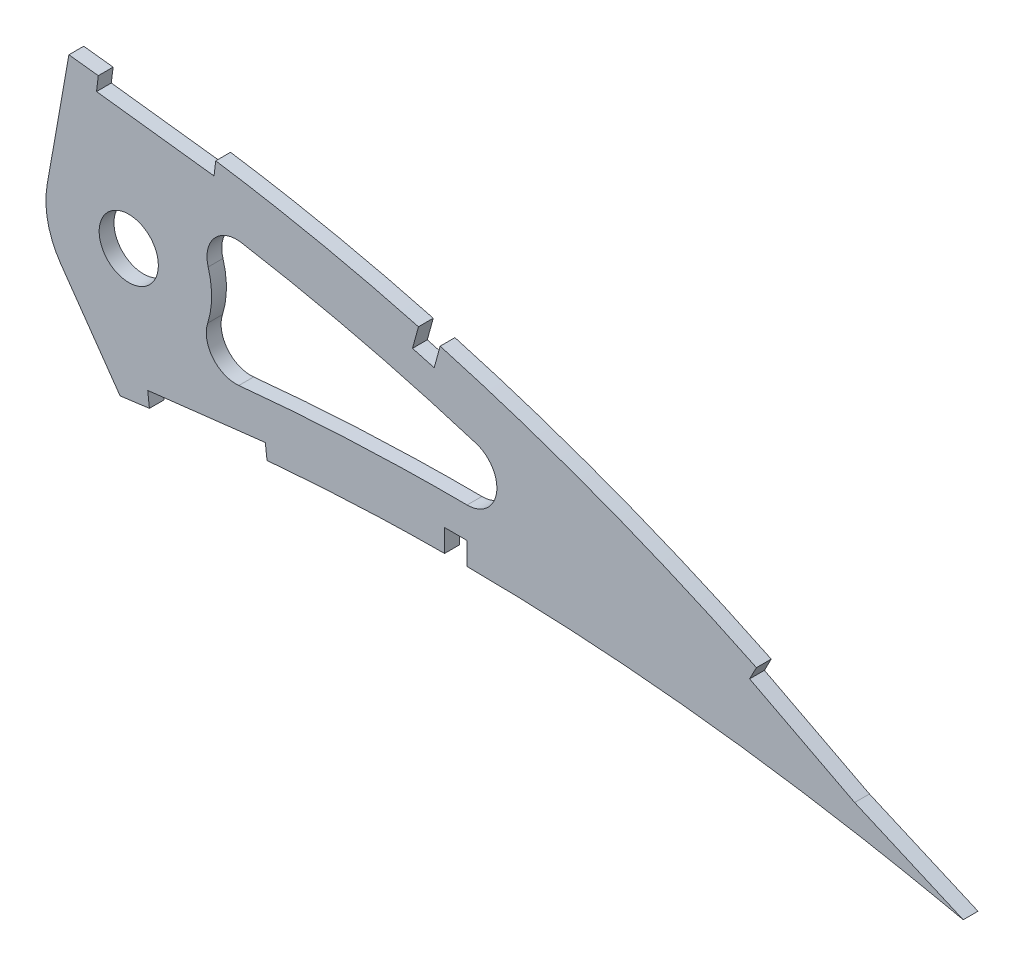
SolidWorks part; units mm, degrees
note: '?' marks a value the reader was unsure of.
material "Pine"
ref_plane "Front Plane" through (0, 0, 0) normal (0, 0, 1) x (1, 0, 0)
ref_plane "Top Plane" through (0, 0, 0) normal (0, 1, 0) x (1, 0, 0)
ref_plane "Right Plane" through (0, 0, 0) normal (1, 0, 0) x (0, 0, -1)
curve "Curve1"
  spline degree 3 poles (554.3197, 0.8642, 0) (554.2772, 0.8904, 0) (554.1075, 0.9953, 0) (553.7252, 1.2298, 0) (553.0885, 1.6204, 0) (552.1972, 2.1644, 0) (551.0519, 2.8603, 0) (549.6522, 3.7033, 0) (547.9988, 4.6906, 0) (546.0922, 5.8176, 0) (543.9326, 7.0789, 0) (541.5207, 8.4695, 0) (538.8569, 9.9815, 0) (535.942, 11.6087, 0) (532.7772, 13.3434, 0) (529.3631, 15.1777, 0) (525.7007, 17.1023, 0) (521.7917, 19.109, 0) (517.6366, 21.1866, 0) (513.2374, 23.3265, 0) (508.5956, 25.518, 0) (503.7128, 27.7495, 0) (498.5918, 30.0118, 0) (493.234, 32.2909, 0) (487.6424, 34.577, 0) (481.8195, 36.8569, 0) (475.7686, 39.1203, 0) (469.4922, 41.3526, 0) (462.9949, 43.5439, 0) (456.2798, 45.6802, 0) (449.3518, 47.7496, 0) (442.2149, 49.739, 0) (434.875, 51.6379, 0) (427.3368, 53.4327, 0) (419.6066, 55.1112, 0) (411.6907, 56.6635, 0) (403.5957, 58.0739, 0) (395.344, 59.3415, 0) (387.0683, 60.3958, 0) (378.8096, 61.4299, 0) (370.5633, 62.4014, 0) (362.2161, 63.3317, 0) (353.7762, 64.2156, 0) (345.252, 65.0503, 0) (336.6519, 65.8323, 0) (327.9851, 66.5592, 0) (319.2598, 67.227, 0) (310.4852, 67.8346, 0) (301.6702, 68.3766, 0) (292.8239, 68.8527, 0) (283.9555, 69.2595, 0) (275.0741, 69.5943, 0) (266.1892, 69.8549, 0) (257.3099, 70.039, 0) (248.446, 70.1454, 0) (239.6066, 70.171, 0) (230.8014, 70.1156, 0) (222.0395, 69.9772, 0) (213.3305, 69.7538, 0) (204.6838, 69.4452, 0) (196.1087, 69.0513, 0) (187.6145, 68.5689, 0) (179.2105, 68.0012, 0) (170.9059, 67.3456, 0) (162.7101, 66.6021, 0) (154.6315, 65.7736, 0) (146.6791, 64.8581, 0) (138.8614, 63.858, 0) (131.1871, 62.7754, 0) (123.6647, 61.6096, 0) (116.3022, 60.3641, 0) (109.1077, 59.04, 0) (102.0887, 57.6413, 0) (95.2529, 56.1683, 0) (88.6074, 54.6255, 0) (82.1593, 53.0155, 0) (75.9155, 51.3413, 0) (69.8822, 49.607, 0) (64.0656, 47.8163, 0) (58.4725, 45.9714, 0) (53.107, 44.0792, 0) (47.9758, 42.141, 0) (43.0829, 40.1629, 0) (38.4338, 38.1474, 0) (34.0322, 36.1008, 0) (29.883, 34.0255, 0) (25.9891, 31.9271, 0) (22.3545, 29.809, 0) (18.9827, 27.675, 0) (15.875, 25.5306, 0) (13.0358, 23.3771, 0) (10.4661, 21.22, 0) (8.1674, 19.0625, 0) (6.143, 16.9061, 0) (4.3929, 14.7547, 0) (2.9194, 12.6099, 0) (1.7228, 10.4738, 0) (0.8056, 8.3479, 0) (0.1671, 6.2334, 0) (-0.1824, 4.1334, 0) (-0.2694, 2.0463, 0) (-0.0897, 0.6811, 0) (0, 0, 0) knots 0 0 0 0 0.000254 0.001015 0.002283 0.004057 0.006331 0.009105 0.012374 0.016134 0.02038 0.025106 0.030306 0.035972 0.0421 0.048678 0.055702 0.06316 0.071046 0.07935 0.088063 0.097176 0.106678 0.116562 0.126814 0.137428 0.148394 0.1597 0.171338 0.183298 0.19557 0.208144 0.221012 0.234162 0.247587 0.261277 0.275223 0.289414 0.303771 0.317689 0.331784 0.34604 0.360444 0.374983 0.38964 0.404403 0.419257 0.434187 0.449177 0.464215 0.479284 0.49437 0.509458 0.524532 0.539579 0.554583 0.56953 0.584403 0.599191 0.613877 0.628447 0.642889 0.657186 0.671326 0.685294 0.699078 0.712665 0.726043 0.739198 0.752118 0.764792 0.777208 0.789356 0.801224 0.812804 0.824083 0.835055 0.84571 0.856038 0.866034 0.875689 0.884998 0.893953 0.902553 0.910789 0.918661 0.926166 0.933303 0.940071 0.946475 0.952518 0.958205 0.963547 0.968557 0.97325 0.977651 0.981787 0.985694 0.989415 0.993001 0.996508 1 1 1 1
curve "Curve2"
  spline degree 3 poles (0, 0, 0) (0.1423, -0.672, 0) (0.4277, -2.019, 0) (1.203, -3.9582, 0) (2.2282, -5.8223, 0) (3.5249, -7.6064, 0) (5.0845, -9.31, 0) (6.9036, -10.9348, 0) (8.9803, -12.4801, 0) (11.3119, -13.945, 0) (13.8951, -15.3312, 0) (16.7269, -16.6378, 0) (19.8048, -17.8643, 0) (23.1254, -19.0092, 0) (26.6846, -20.0741, 0) (30.4791, -21.0566, 0) (34.5045, -21.9578, 0) (38.7571, -22.7757, 0) (43.232, -23.5109, 0) (47.9248, -24.1631, 0) (52.8305, -24.7327, 0) (57.9444, -25.2185, 0) (63.2614, -25.6215, 0) (68.7762, -25.942, 0) (74.4834, -26.1811, 0) (80.3777, -26.3377, 0) (86.4531, -26.4144, 0) (92.7043, -26.4123, 0) (99.1251, -26.3308, 0) (105.71, -26.1745, 0) (112.4527, -25.9423, 0) (119.3471, -25.6371, 0) (126.387, -25.2619, 0) (133.5661, -24.818, 0) (140.8781, -24.3074, 0) (148.3166, -23.7341, 0) (155.8748, -23.0997, 0) (163.5462, -22.4077, 0) (171.324, -21.6617, 0) (179.2015, -20.864, 0) (187.1716, -20.0183, 0) (195.2274, -19.1275, 0) (203.3619, -18.1963, 0) (211.5677, -17.2262, 0) (219.8379, -16.223, 0) (228.1647, -15.1885, 0) (236.5412, -14.1266, 0) (244.9597, -13.0425, 0) (253.4125, -11.9359, 0) (261.8924, -10.8148, 0) (270.3912, -9.6781, 0) (278.9016, -8.5319, 0) (287.4156, -7.3796, 0) (295.925, -6.2216, 0) (304.4222, -5.0626, 0) (312.8995, -3.9059, 0) (321.3485, -2.7516, 0) (329.7616, -1.6054, 0) (338.1302, -0.4672, 0) (346.4467, 0.6607, 0) (354.7031, 1.775, 0) (362.8916, 2.8743, 0) (371.0037, 3.9578, 0) (379.0314, 5.0259, 0) (386.8463, 6.0463, 0) (394.4281, 7.0733, 0) (401.8022, 7.9152, 0) (409.0845, 8.6338, 0) (416.2825, 9.2229, 0) (423.3877, 9.6911, 0) (430.3918, 10.0417, 0) (437.2865, 10.2795, 0) (444.0631, 10.4116, 0) (450.7132, 10.4414, 0) (457.2276, 10.3785, 0) (463.598, 10.2277, 0) (469.8153, 9.9961, 0) (475.8709, 9.6912, 0) (481.7563, 9.3216, 0) (487.4626, 8.8925, 0) (492.9818, 8.4141, 0) (498.3055, 7.8933, 0) (503.4254, 7.336, 0) (508.334, 6.7541, 0) (513.0236, 6.1512, 0) (517.4871, 5.5374, 0) (521.7172, 4.9187, 0) (525.7074, 4.3032, 0) (529.4512, 3.6966, 0) (532.9427, 3.1071, 0) (536.1764, 2.5402, 0) (539.1467, 2.0013, 0) (541.8495, 1.4973, 0) (544.2794, 1.0307, 0) (546.4331, 0.6092, 0) (548.3068, 0.2346, 0) (549.8976, -0.0878, 0) (551.2027, -0.3567, 0) (552.2202, -0.5677, 0) (552.948, -0.7211, 0) (553.3854, -0.8124, 0) (553.5798, -0.8538, 0) (553.6283, -0.8642, 0) knots 0 0 0 0 0.003638 0.007293 0.011028 0.014901 0.018963 0.023258 0.027821 0.032679 0.037853 0.043362 0.049215 0.055422 0.061989 0.068918 0.076211 0.083868 0.091887 0.100266 0.109 0.118085 0.127515 0.137285 0.147388 0.157816 0.168563 0.179619 0.190977 0.202627 0.21456 0.226767 0.239236 0.251959 0.264924 0.27812 0.291536 0.30516 0.318981 0.332985 0.347163 0.361499 0.375981 0.390597 0.405333 0.420175 0.43511 0.450124 0.465203 0.480333 0.495501 0.51069 0.525887 0.541078 0.556247 0.571382 0.586466 0.601485 0.616424 0.631269 0.646007 0.660621 0.675098 0.689423 0.703582 0.716908 0.730009 0.742952 0.755726 0.76832 0.780724 0.792927 0.804916 0.816679 0.828204 0.839475 0.850481 0.861208 0.871639 0.881763 0.891564 0.901027 0.910139 0.918884 0.927249 0.935221 0.942785 0.949928 0.956638 0.962904 0.968712 0.974054 0.978918 0.983297 0.98718 0.990561 0.993433 0.995791 0.99763 0.998946 0.999737 1 1 1 1
sketch "Sketch1" plane through (0, 0, 0) normal (0, 0, 1) x (1, 0, 0)
  line L28 (0, 63.5) -> (-23.1981, 63.5) construction
  line L39 (379.9183, -27.3345) -> (379.9183, 27.3345) construction
  line L40 (379.9183, 61.2846) -> (364.3182, 3.0643) construction
  line L41 (554.3197, 0.8642) -> (558.9578, -2.001)
  line L42 (553.6283, -0.8642) -> (558.9578, -2.001)
  circle A0 centre (68.58, 6.35) radius 9.525 construction
  circle A1 centre (246.38, 6.35) radius 9.525 construction
  spline S2 degree 3 poles (-4831.4743, -1278.9049) (97.0525, 89.5296) (-10.8205, 26.1166) (1.203, -3.9582) (2.2282, -5.8223) (3.5249, -7.6064) (5.0845, -9.31) (6.9036, -10.9348) (8.9803, -12.4801) (11.3119, -13.945) (13.8951, -15.3312) (16.7269, -16.6378) (19.8048, -17.8643) (23.1254, -19.0092) (26.6846, -20.0741) (30.4791, -21.0566) (34.5045, -21.9578) (38.7571, -22.7757) (43.232, -23.5109) (47.9248, -24.1631) (52.8305, -24.7327) (57.9444, -25.2185) (63.2614, -25.6215) (68.7762, -25.942) (74.4834, -26.1811) (80.3777, -26.3377) (86.4531, -26.4144) (92.7043, -26.4123) (99.1251, -26.3308) (105.71, -26.1745) (112.4527, -25.9423) (119.3471, -25.6371) (126.387, -25.2619) (133.5661, -24.818) (140.8781, -24.3074) (148.3166, -23.7341) (155.8748, -23.0997) (163.5462, -22.4077) (171.324, -21.6617) (179.2015, -20.864) (187.1716, -20.0183) (195.2274, -19.1275) (203.3619, -18.1963) (211.5677, -17.2262) (219.8379, -16.223) (228.1647, -15.1885) (236.5412, -14.1266) (244.9597, -13.0425) (253.4125, -11.9359) (261.8924, -10.8148) (270.3912, -9.6781) (278.9016, -8.5319) (287.4156, -7.3796) (295.925, -6.2216) (304.4222, -5.0626) (312.8995, -3.9059) (321.3485, -2.7516) (329.7616, -1.6054) (338.1302, -0.4672) (346.4467, 0.6607) (354.7031, 1.775) (362.8916, 2.8743) (371.0037, 3.9578) (379.0314, 5.0259) (386.8463, 6.0463) (394.4281, 7.0733) (401.8022, 7.9152) (409.0845, 8.6338) (416.2825, 9.2229) (423.3877, 9.6911) (430.3918, 10.0417) (437.2865, 10.2795) (444.0631, 10.4116) (450.7132, 10.4414) (457.2276, 10.3785) (463.598, 10.2277) (469.8153, 9.9961) (475.8709, 9.6912) (481.7563, 9.3216) (487.4626, 8.8925) (492.9818, 8.4141) (498.3055, 7.8933) (503.4254, 7.336) (508.334, 6.7541) (513.0236, 6.1512) (517.4871, 5.5374) (521.7172, 4.9187) (525.7074, 4.3032) (529.4512, 3.6966) (532.9427, 3.1071) (536.1764, 2.5402) (539.1467, 2.0013) (541.8495, 1.4973) (544.2794, 1.0307) (546.4331, 0.6092) (548.3068, 0.2346) (549.8976, -0.0878) (551.2027, -0.3567) (552.2202, -0.5677) (552.948, -0.7211) (575.3009, -5.3866) (595.0764, -21.0399) (1653.4451, 4874.9179) knots -0.160008 -0.160008 -0.160008 -0.160008 0.003638 0.007293 0.011028 0.014901 0.018963 0.023258 0.027821 0.032679 0.037853 0.043362 0.049215 0.055422 0.061989 0.068918 0.076211 0.083868 0.091887 0.100266 0.109 0.118085 0.127515 0.137285 0.147388 0.157816 0.168563 0.179619 0.190977 0.202627 0.21456 0.226767 0.239236 0.251959 0.264924 0.27812 0.291536 0.30516 0.318981 0.332985 0.347163 0.361499 0.375981 0.390597 0.405333 0.420175 0.43511 0.450124 0.465203 0.480333 0.495501 0.51069 0.525887 0.541078 0.556247 0.571382 0.586466 0.601485 0.616424 0.631269 0.646007 0.660621 0.675098 0.689423 0.703582 0.716908 0.730009 0.742952 0.755726 0.76832 0.780724 0.792927 0.804916 0.816679 0.828204 0.839475 0.850481 0.861208 0.871639 0.881763 0.891564 0.901027 0.910139 0.918884 0.927249 0.935221 0.942785 0.949928 0.956638 0.962904 0.968712 0.974054 0.978918 0.983297 0.98718 0.990561 0.993433 0.995791 0.99763 0.998946 0.999737 1.118764 1.118764 1.118764 1.118764 only from (0, 0) to (553.6283, -0.8642) construction
  spline S3 degree 3 poles (0, 0) (0.1423, -0.672) (0.4277, -2.019) (1.203, -3.9582) (2.2282, -5.8223) (3.5249, -7.6064) (5.0845, -9.31) (6.9036, -10.9348) (8.9803, -12.4801) (11.3119, -13.945) (13.8951, -15.3312) (16.7269, -16.6378) (19.8048, -17.8643) (23.1254, -19.0092) (26.6846, -20.0741) (30.4791, -21.0566) (34.5045, -21.9578) (38.7571, -22.7757) (43.232, -23.5109) (47.9248, -24.1631) (52.8305, -24.7327) (57.9444, -25.2185) (63.2614, -25.6215) (68.7762, -25.942) (74.4834, -26.1811) (80.3777, -26.3377) (86.4531, -26.4144) (92.7043, -26.4123) (99.1251, -26.3308) (105.71, -26.1745) (112.4527, -25.9423) (119.3471, -25.6371) (126.387, -25.2619) (133.5661, -24.818) (140.8781, -24.3074) (148.3166, -23.7341) (155.8748, -23.0997) (163.5462, -22.4077) (171.324, -21.6617) (179.2015, -20.864) (187.1716, -20.0183) (195.2274, -19.1275) (203.3619, -18.1963) (211.5677, -17.2262) (219.8379, -16.223) (228.1647, -15.1885) (236.5412, -14.1266) (244.9597, -13.0425) (253.4125, -11.9359) (261.8924, -10.8148) (270.3912, -9.6781) (278.9016, -8.5319) (287.4156, -7.3796) (295.925, -6.2216) (304.4222, -5.0626) (312.8995, -3.9059) (321.3485, -2.7516) (329.7616, -1.6054) (338.1302, -0.4672) (346.4467, 0.6607) (354.7031, 1.775) (362.8916, 2.8743) (371.0037, 3.9578) (379.0314, 5.0259) (386.8463, 6.0463) (394.4281, 7.0733) (401.8022, 7.9152) (409.0845, 8.6338) (416.2825, 9.2229) (423.3877, 9.6911) (430.3918, 10.0417) (437.2865, 10.2795) (444.0631, 10.4116) (450.7132, 10.4414) (457.2276, 10.3785) (463.598, 10.2277) (469.8153, 9.9961) (475.8709, 9.6912) (481.7563, 9.3216) (487.4626, 8.8925) (492.9818, 8.4141) (498.3055, 7.8933) (503.4254, 7.336) (508.334, 6.7541) (513.0236, 6.1512) (517.4871, 5.5374) (521.7172, 4.9187) (525.7074, 4.3032) (529.4512, 3.6966) (532.9427, 3.1071) (536.1764, 2.5402) (539.1467, 2.0013) (541.8495, 1.4973) (544.2794, 1.0307) (546.4331, 0.6092) (548.3068, 0.2346) (549.8976, -0.0878) (551.2027, -0.3567) (552.2202, -0.5677) (552.948, -0.7211) (553.3854, -0.8124) (553.5798, -0.8538) (553.6283, -0.8642) knots 0 0 0 0 0.003638 0.007293 0.011028 0.014901 0.018963 0.023258 0.027821 0.032679 0.037853 0.043362 0.049215 0.055422 0.061989 0.068918 0.076211 0.083868 0.091887 0.100266 0.109 0.118085 0.127515 0.137285 0.147388 0.157816 0.168563 0.179619 0.190977 0.202627 0.21456 0.226767 0.239236 0.251959 0.264924 0.27812 0.291536 0.30516 0.318981 0.332985 0.347163 0.361499 0.375981 0.390597 0.405333 0.420175 0.43511 0.450124 0.465203 0.480333 0.495501 0.51069 0.525887 0.541078 0.556247 0.571382 0.586466 0.601485 0.616424 0.631269 0.646007 0.660621 0.675098 0.689423 0.703582 0.716908 0.730009 0.742952 0.755726 0.76832 0.780724 0.792927 0.804916 0.816679 0.828204 0.839475 0.850481 0.861208 0.871639 0.881763 0.891564 0.901027 0.910139 0.918884 0.927249 0.935221 0.942785 0.949928 0.956638 0.962904 0.968712 0.974054 0.978918 0.983297 0.98718 0.990561 0.993433 0.995791 0.99763 0.998946 0.999737 1 1 1 1
  spline S4 degree 3 poles (3239.7341, 4216.6854) (591.6583, -33.9123) (575.4525, -12.0974) (553.7252, 1.2298) (553.0885, 1.6204) (552.1972, 2.1644) (551.0519, 2.8603) (549.6522, 3.7033) (547.9988, 4.6906) (546.0922, 5.8176) (543.9326, 7.0789) (541.5207, 8.4695) (538.8569, 9.9815) (535.942, 11.6087) (532.7772, 13.3434) (529.3631, 15.1777) (525.7007, 17.1023) (521.7917, 19.109) (517.6366, 21.1866) (513.2374, 23.3265) (508.5956, 25.518) (503.7128, 27.7495) (498.5918, 30.0118) (493.234, 32.2909) (487.6424, 34.577) (481.8195, 36.8569) (475.7686, 39.1203) (469.4922, 41.3526) (462.9949, 43.5439) (456.2798, 45.6802) (449.3518, 47.7496) (442.2149, 49.739) (434.875, 51.6379) (427.3368, 53.4327) (419.6066, 55.1112) (411.6907, 56.6635) (403.5957, 58.0739) (395.344, 59.3415) (387.0683, 60.3958) (378.8096, 61.4299) (370.5633, 62.4014) (362.2161, 63.3317) (353.7762, 64.2156) (345.252, 65.0503) (336.6519, 65.8323) (327.9851, 66.5592) (319.2598, 67.227) (310.4852, 67.8346) (301.6702, 68.3766) (292.8239, 68.8527) (283.9555, 69.2595) (275.0741, 69.5943) (266.1892, 69.8549) (257.3099, 70.039) (248.446, 70.1454) (239.6066, 70.171) (230.8014, 70.1156) (222.0395, 69.9772) (213.3305, 69.7538) (204.6838, 69.4452) (196.1087, 69.0513) (187.6145, 68.5689) (179.2105, 68.0012) (170.9059, 67.3456) (162.7101, 66.6021) (154.6315, 65.7736) (146.6791, 64.8581) (138.8614, 63.858) (131.1871, 62.7754) (123.6647, 61.6096) (116.3022, 60.3641) (109.1077, 59.04) (102.0887, 57.6413) (95.2529, 56.1683) (88.6074, 54.6255) (82.1593, 53.0155) (75.9155, 51.3413) (69.8822, 49.607) (64.0656, 47.8163) (58.4725, 45.9714) (53.107, 44.0792) (47.9758, 42.141) (43.0829, 40.1629) (38.4338, 38.1474) (34.0322, 36.1008) (29.883, 34.0255) (25.9891, 31.9271) (22.3545, 29.809) (18.9827, 27.675) (15.875, 25.5306) (13.0358, 23.3771) (10.4661, 21.22) (8.1674, 19.0625) (6.143, 16.9061) (4.3929, 14.7547) (2.9194, 12.6099) (1.7228, 10.4738) (0.8056, 8.3479) (0.1671, 6.2334) (-0.1824, 4.1334) (-1.529, -28.173) (121.5517, -52.0111) (-4981.9447, -401.2454) knots -0.12747 -0.12747 -0.12747 -0.12747 0.000254 0.001015 0.002283 0.004057 0.006331 0.009105 0.012374 0.016134 0.02038 0.025106 0.030306 0.035972 0.0421 0.048678 0.055702 0.06316 0.071046 0.07935 0.088063 0.097176 0.106678 0.116562 0.126814 0.137428 0.148394 0.1597 0.171338 0.183298 0.19557 0.208144 0.221012 0.234162 0.247587 0.261277 0.275223 0.289414 0.303771 0.317689 0.331784 0.34604 0.360444 0.374983 0.38964 0.404403 0.419257 0.434187 0.449177 0.464215 0.479284 0.49437 0.509458 0.524532 0.539579 0.554583 0.56953 0.584403 0.599191 0.613877 0.628447 0.642889 0.657186 0.671326 0.685294 0.699078 0.712665 0.726043 0.739198 0.752118 0.764792 0.777208 0.789356 0.801224 0.812804 0.824083 0.835055 0.84571 0.856038 0.866034 0.875689 0.884998 0.893953 0.902553 0.910789 0.918661 0.926166 0.933303 0.940071 0.946475 0.952518 0.958205 0.963547 0.968557 0.97325 0.977651 0.981787 0.985694 0.989415 0.993001 0.996508 1.153258 1.153258 1.153258 1.153258 only from (554.3197, 0.8642) to (0, 0) construction
  spline S6 degree 3 poles (554.3197, 0.8642) (554.2772, 0.8904) (554.1075, 0.9953) (553.7252, 1.2298) (553.0885, 1.6204) (552.1972, 2.1644) (551.0519, 2.8603) (549.6522, 3.7033) (547.9988, 4.6906) (546.0922, 5.8176) (543.9326, 7.0789) (541.5207, 8.4695) (538.8569, 9.9815) (535.942, 11.6087) (532.7772, 13.3434) (529.3631, 15.1777) (525.7007, 17.1023) (521.7917, 19.109) (517.6366, 21.1866) (513.2374, 23.3265) (508.5956, 25.518) (503.7128, 27.7495) (498.5918, 30.0118) (493.234, 32.2909) (487.6424, 34.577) (481.8195, 36.8569) (475.7686, 39.1203) (469.4922, 41.3526) (462.9949, 43.5439) (456.2798, 45.6802) (449.3518, 47.7496) (442.2149, 49.739) (434.875, 51.6379) (427.3368, 53.4327) (419.6066, 55.1112) (411.6907, 56.6635) (403.5957, 58.0739) (395.344, 59.3415) (387.0683, 60.3958) (378.8096, 61.4299) (370.5633, 62.4014) (362.2161, 63.3317) (353.7762, 64.2156) (345.252, 65.0503) (336.6519, 65.8323) (327.9851, 66.5592) (319.2598, 67.227) (310.4852, 67.8346) (301.6702, 68.3766) (292.8239, 68.8527) (283.9555, 69.2595) (275.0741, 69.5943) (266.1892, 69.8549) (257.3099, 70.039) (248.446, 70.1454) (239.6066, 70.171) (230.8014, 70.1156) (222.0395, 69.9772) (213.3305, 69.7538) (204.6838, 69.4452) (196.1087, 69.0513) (187.6145, 68.5689) (179.2105, 68.0012) (170.9059, 67.3456) (162.7101, 66.6021) (154.6315, 65.7736) (146.6791, 64.8581) (138.8614, 63.858) (131.1871, 62.7754) (123.6647, 61.6096) (116.3022, 60.3641) (109.1077, 59.04) (102.0887, 57.6413) (95.2529, 56.1683) (88.6074, 54.6255) (82.1593, 53.0155) (75.9155, 51.3413) (69.8822, 49.607) (64.0656, 47.8163) (58.4725, 45.9714) (53.107, 44.0792) (47.9758, 42.141) (43.0829, 40.1629) (38.4338, 38.1474) (34.0322, 36.1008) (29.883, 34.0255) (25.9891, 31.9271) (22.3545, 29.809) (18.9827, 27.675) (15.875, 25.5306) (13.0358, 23.3771) (10.4661, 21.22) (8.1674, 19.0625) (6.143, 16.9061) (4.3929, 14.7547) (2.9194, 12.6099) (1.7228, 10.4738) (0.8056, 8.3479) (0.1671, 6.2334) (-0.1824, 4.1334) (-0.2694, 2.0463) (-0.0897, 0.6811) (0, 0) knots 0 0 0 0 0.000254 0.001015 0.002283 0.004057 0.006331 0.009105 0.012374 0.016134 0.02038 0.025106 0.030306 0.035972 0.0421 0.048678 0.055702 0.06316 0.071046 0.07935 0.088063 0.097176 0.106678 0.116562 0.126814 0.137428 0.148394 0.1597 0.171338 0.183298 0.19557 0.208144 0.221012 0.234162 0.247587 0.261277 0.275223 0.289414 0.303771 0.317689 0.331784 0.34604 0.360444 0.374983 0.38964 0.404403 0.419257 0.434187 0.449177 0.464215 0.479284 0.49437 0.509458 0.524532 0.539579 0.554583 0.56953 0.584403 0.599191 0.613877 0.628447 0.642889 0.657186 0.671326 0.685294 0.699078 0.712665 0.726043 0.739198 0.752118 0.764792 0.777208 0.789356 0.801224 0.812804 0.824083 0.835055 0.84571 0.856038 0.866034 0.875689 0.884998 0.893953 0.902553 0.910789 0.918661 0.926166 0.933303 0.940071 0.946475 0.952518 0.958205 0.963547 0.968557 0.97325 0.977651 0.981787 0.985694 0.989415 0.993001 0.996508 1 1 1 1
  point P10 (81.0487, 17.1134)
  point P11 (234.9492, 33.5094)
  dimension "D2" = 19.05
  dimension "D18" = 177.8
  dimension "D3" = 15
  dimension "D5" = 63.5
  dimension "D7" = 57.15
  dimension "D12" = 57.15
  dimension "D17" = 68.58
extrude "Boss-Extrude1" add sketch "Sketch1" along normal blind 3.175
sketch "Sketch2" plane through (0, 0, 3.175) normal (0, 0, 1) x (1, 0, 0)
  line L0 (362.4084, 36.32) -> (367.0753, 62.7877)
  line L5 (365.3537, 23.0344) -> (378.0559, 4.8939)
  line L6 (379.9183, 33.2326) -> (412.5731, 33.2326) construction
  circle A4 centre (379.9183, 33.2326) radius 17.78
  circle A10 centre (379.9183, 33.2326) radius 6.35
  spline S0 degree 3 poles (-1940.5458, -482.1449) (50.3561, 59.7807) (-7.8624, 18.7173) (1.203, -3.9582) (2.2282, -5.8223) (3.5249, -7.6064) (5.0845, -9.31) (6.9036, -10.9348) (8.9803, -12.4801) (11.3119, -13.945) (13.8951, -15.3312) (16.7269, -16.6378) (19.8048, -17.8643) (23.1254, -19.0092) (26.6846, -20.0741) (30.4791, -21.0566) (34.5045, -21.9578) (38.7571, -22.7757) (43.232, -23.5109) (47.9248, -24.1631) (52.8305, -24.7327) (57.9444, -25.2185) (63.2614, -25.6215) (68.7762, -25.942) (74.4834, -26.1811) (80.3777, -26.3377) (86.4531, -26.4144) (92.7043, -26.4123) (99.1251, -26.3308) (105.71, -26.1745) (112.4527, -25.9423) (119.3471, -25.6371) (126.387, -25.2619) (133.5661, -24.818) (140.8781, -24.3074) (148.3166, -23.7341) (155.8748, -23.0997) (163.5462, -22.4077) (171.324, -21.6617) (179.2015, -20.864) (187.1716, -20.0183) (195.2274, -19.1275) (203.3619, -18.1963) (211.5677, -17.2262) (219.8379, -16.223) (228.1647, -15.1885) (236.5412, -14.1266) (244.9597, -13.0425) (253.4125, -11.9359) (261.8924, -10.8148) (270.3912, -9.6781) (278.9016, -8.5319) (287.4156, -7.3796) (295.925, -6.2216) (304.4222, -5.0626) (312.8995, -3.9059) (321.3485, -2.7516) (329.7616, -1.6054) (338.1302, -0.4672) (346.4467, 0.6607) (354.7031, 1.775) (362.8916, 2.8743) (371.0037, 3.9578) (379.0314, 5.0259) (386.8463, 6.0463) (394.4281, 7.0733) (401.8022, 7.9152) (409.0845, 8.6338) (416.2825, 9.2229) (423.3877, 9.6911) (430.3918, 10.0417) (437.2865, 10.2795) (444.0631, 10.4116) (450.7132, 10.4414) (457.2276, 10.3785) (463.598, 10.2277) (469.8153, 9.9961) (475.8709, 9.6912) (481.7563, 9.3216) (487.4626, 8.8925) (492.9818, 8.4141) (498.3055, 7.8933) (503.4254, 7.336) (508.334, 6.7541) (513.0236, 6.1512) (517.4871, 5.5374) (521.7172, 4.9187) (525.7074, 4.3032) (529.4512, 3.6966) (532.9427, 3.1071) (536.1764, 2.5402) (539.1467, 2.0013) (541.8495, 1.4973) (544.2794, 1.0307) (546.4331, 0.6092) (548.3068, 0.2346) (549.8976, -0.0878) (551.2027, -0.3567) (552.2202, -0.5677) (552.948, -0.7211) (569.5328, -4.1827) (584.5994, -13.6239) (1015.6751, 1944.7152) knots -0.117928 -0.117928 -0.117928 -0.117928 0.003638 0.007293 0.011028 0.014901 0.018963 0.023258 0.027821 0.032679 0.037853 0.043362 0.049215 0.055422 0.061989 0.068918 0.076211 0.083868 0.091887 0.100266 0.109 0.118085 0.127515 0.137285 0.147388 0.157816 0.168563 0.179619 0.190977 0.202627 0.21456 0.226767 0.239236 0.251959 0.264924 0.27812 0.291536 0.30516 0.318981 0.332985 0.347163 0.361499 0.375981 0.390597 0.405333 0.420175 0.43511 0.450124 0.465203 0.480333 0.495501 0.51069 0.525887 0.541078 0.556247 0.571382 0.586466 0.601485 0.616424 0.631269 0.646007 0.660621 0.675098 0.689423 0.703582 0.716908 0.730009 0.742952 0.755726 0.76832 0.780724 0.792927 0.804916 0.816679 0.828204 0.839475 0.850481 0.861208 0.871639 0.881763 0.891564 0.901027 0.910139 0.918884 0.927249 0.935221 0.942785 0.949928 0.956638 0.962904 0.968712 0.974054 0.978918 0.983297 0.98718 0.990561 0.993433 0.995791 0.99763 0.998946 0.999737 1.087506 1.087506 1.087506 1.087506 only from (0, 0) to (553.6283, -0.8642) construction
  spline S1 degree 3 poles (1649.7869, 1673.5394) (582.8314, -23.1055) (569.8335, -8.6508) (553.7252, 1.2298) (553.0885, 1.6204) (552.1972, 2.1644) (551.0519, 2.8603) (549.6522, 3.7033) (547.9988, 4.6906) (546.0922, 5.8176) (543.9326, 7.0789) (541.5207, 8.4695) (538.8569, 9.9815) (535.942, 11.6087) (532.7772, 13.3434) (529.3631, 15.1777) (525.7007, 17.1023) (521.7917, 19.109) (517.6366, 21.1866) (513.2374, 23.3265) (508.5956, 25.518) (503.7128, 27.7495) (498.5918, 30.0118) (493.234, 32.2909) (487.6424, 34.577) (481.8195, 36.8569) (475.7686, 39.1203) (469.4922, 41.3526) (462.9949, 43.5439) (456.2798, 45.6802) (449.3518, 47.7496) (442.2149, 49.739) (434.875, 51.6379) (427.3368, 53.4327) (419.6066, 55.1112) (411.6907, 56.6635) (403.5957, 58.0739) (395.344, 59.3415) (387.0683, 60.3958) (378.8096, 61.4299) (370.5633, 62.4014) (362.2161, 63.3317) (353.7762, 64.2156) (345.252, 65.0503) (336.6519, 65.8323) (327.9851, 66.5592) (319.2598, 67.227) (310.4852, 67.8346) (301.6702, 68.3766) (292.8239, 68.8527) (283.9555, 69.2595) (275.0741, 69.5943) (266.1892, 69.8549) (257.3099, 70.039) (248.446, 70.1454) (239.6066, 70.171) (230.8014, 70.1156) (222.0395, 69.9772) (213.3305, 69.7538) (204.6838, 69.4452) (196.1087, 69.0513) (187.6145, 68.5689) (179.2105, 68.0012) (170.9059, 67.3456) (162.7101, 66.6021) (154.6315, 65.7736) (146.6791, 64.8581) (138.8614, 63.858) (131.1871, 62.7754) (123.6647, 61.6096) (116.3022, 60.3641) (109.1077, 59.04) (102.0887, 57.6413) (95.2529, 56.1683) (88.6074, 54.6255) (82.1593, 53.0155) (75.9155, 51.3413) (69.8822, 49.607) (64.0656, 47.8163) (58.4725, 45.9714) (53.107, 44.0792) (47.9758, 42.141) (43.0829, 40.1629) (38.4338, 38.1474) (34.0322, 36.1008) (29.883, 34.0255) (25.9891, 31.9271) (22.3545, 29.809) (18.9827, 27.675) (15.875, 25.5306) (13.0358, 23.3771) (10.4661, 21.22) (8.1674, 19.0625) (6.143, 16.9061) (4.3929, 14.7547) (2.9194, 12.6099) (1.7228, 10.4738) (0.8056, 8.3479) (0.1671, 6.2334) (-0.1824, 4.1334) (-1.1977, -20.225) (67.5062, -39.5284) (-1990.2908, -190.8143) knots -0.093914 -0.093914 -0.093914 -0.093914 0.000254 0.001015 0.002283 0.004057 0.006331 0.009105 0.012374 0.016134 0.02038 0.025106 0.030306 0.035972 0.0421 0.048678 0.055702 0.06316 0.071046 0.07935 0.088063 0.097176 0.106678 0.116562 0.126814 0.137428 0.148394 0.1597 0.171338 0.183298 0.19557 0.208144 0.221012 0.234162 0.247587 0.261277 0.275223 0.289414 0.303771 0.317689 0.331784 0.34604 0.360444 0.374983 0.38964 0.404403 0.419257 0.434187 0.449177 0.464215 0.479284 0.49437 0.509458 0.524532 0.539579 0.554583 0.56953 0.584403 0.599191 0.613877 0.628447 0.642889 0.657186 0.671326 0.685294 0.699078 0.712665 0.726043 0.739198 0.752118 0.764792 0.777208 0.789356 0.801224 0.812804 0.824083 0.835055 0.84571 0.856038 0.866034 0.875689 0.884998 0.893953 0.902553 0.910789 0.918661 0.926166 0.933303 0.940071 0.946475 0.952518 0.958205 0.963547 0.968557 0.97325 0.977651 0.981787 0.985694 0.989415 0.993001 0.996508 1.11295 1.11295 1.11295 1.11295 only from (554.3197, 0.8642) to (0, 0) construction
  spline S2 degree 3 poles (0, 0) (0.1423, -0.672) (0.4277, -2.019) (1.203, -3.9582) (2.2282, -5.8223) (3.5249, -7.6064) (5.0845, -9.31) (6.9036, -10.9348) (8.9803, -12.4801) (11.3119, -13.945) (13.8951, -15.3312) (16.7269, -16.6378) (19.8048, -17.8643) (23.1254, -19.0092) (26.6846, -20.0741) (30.4791, -21.0566) (34.5045, -21.9578) (38.7571, -22.7757) (43.232, -23.5109) (47.9248, -24.1631) (52.8305, -24.7327) (57.9444, -25.2185) (63.2614, -25.6215) (68.7762, -25.942) (74.4834, -26.1811) (80.3777, -26.3377) (86.4531, -26.4144) (92.7043, -26.4123) (99.1251, -26.3308) (105.71, -26.1745) (112.4527, -25.9423) (119.3471, -25.6371) (126.387, -25.2619) (133.5661, -24.818) (140.8781, -24.3074) (148.3166, -23.7341) (155.8748, -23.0997) (163.5462, -22.4077) (171.324, -21.6617) (179.2015, -20.864) (187.1716, -20.0183) (195.2274, -19.1275) (203.3619, -18.1963) (211.5677, -17.2262) (219.8379, -16.223) (228.1647, -15.1885) (236.5412, -14.1266) (244.9597, -13.0425) (253.4125, -11.9359) (261.8924, -10.8148) (270.3912, -9.6781) (278.9016, -8.5319) (287.4156, -7.3796) (295.925, -6.2216) (304.4222, -5.0626) (312.8995, -3.9059) (321.3485, -2.7516) (329.7616, -1.6054) (338.1302, -0.4672) (346.4467, 0.6607) (354.7031, 1.775) (362.8916, 2.8743) (371.0037, 3.9578) (379.0314, 5.0259) (386.8463, 6.0463) (394.4281, 7.0733) (401.8022, 7.9152) (409.0845, 8.6338) (416.2825, 9.2229) (423.3877, 9.6911) (430.3918, 10.0417) (437.2865, 10.2795) (444.0631, 10.4116) (450.7132, 10.4414) (457.2276, 10.3785) (463.598, 10.2277) (469.8153, 9.9961) (475.8709, 9.6912) (481.7563, 9.3216) (487.4626, 8.8925) (492.9818, 8.4141) (498.3055, 7.8933) (503.4254, 7.336) (508.334, 6.7541) (513.0236, 6.1512) (517.4871, 5.5374) (521.7172, 4.9187) (525.7074, 4.3032) (529.4512, 3.6966) (532.9427, 3.1071) (536.1764, 2.5402) (539.1467, 2.0013) (541.8495, 1.4973) (544.2794, 1.0307) (546.4331, 0.6092) (548.3068, 0.2346) (549.8976, -0.0878) (551.2027, -0.3567) (552.2202, -0.5677) (552.948, -0.7211) (553.3854, -0.8124) (553.5798, -0.8538) (553.6283, -0.8642) knots 0 0 0 0 0.003638 0.007293 0.011028 0.014901 0.018963 0.023258 0.027821 0.032679 0.037853 0.043362 0.049215 0.055422 0.061989 0.068918 0.076211 0.083868 0.091887 0.100266 0.109 0.118085 0.127515 0.137285 0.147388 0.157816 0.168563 0.179619 0.190977 0.202627 0.21456 0.226767 0.239236 0.251959 0.264924 0.27812 0.291536 0.30516 0.318981 0.332985 0.347163 0.361499 0.375981 0.390597 0.405333 0.420175 0.43511 0.450124 0.465203 0.480333 0.495501 0.51069 0.525887 0.541078 0.556247 0.571382 0.586466 0.601485 0.616424 0.631269 0.646007 0.660621 0.675098 0.689423 0.703582 0.716908 0.730009 0.742952 0.755726 0.76832 0.780724 0.792927 0.804916 0.816679 0.828204 0.839475 0.850481 0.861208 0.871639 0.881763 0.891564 0.901027 0.910139 0.918884 0.927249 0.935221 0.942785 0.949928 0.956638 0.962904 0.968712 0.974054 0.978918 0.983297 0.98718 0.990561 0.993433 0.995791 0.99763 0.998946 0.999737 1 1 1 1
  spline S3 degree 3 poles (554.3197, 0.8642) (554.2772, 0.8904) (554.1075, 0.9953) (553.7252, 1.2298) (553.0885, 1.6204) (552.1972, 2.1644) (551.0519, 2.8603) (549.6522, 3.7033) (547.9988, 4.6906) (546.0922, 5.8176) (543.9326, 7.0789) (541.5207, 8.4695) (538.8569, 9.9815) (535.942, 11.6087) (532.7772, 13.3434) (529.3631, 15.1777) (525.7007, 17.1023) (521.7917, 19.109) (517.6366, 21.1866) (513.2374, 23.3265) (508.5956, 25.518) (503.7128, 27.7495) (498.5918, 30.0118) (493.234, 32.2909) (487.6424, 34.577) (481.8195, 36.8569) (475.7686, 39.1203) (469.4922, 41.3526) (462.9949, 43.5439) (456.2798, 45.6802) (449.3518, 47.7496) (442.2149, 49.739) (434.875, 51.6379) (427.3368, 53.4327) (419.6066, 55.1112) (411.6907, 56.6635) (403.5957, 58.0739) (395.344, 59.3415) (387.0683, 60.3958) (378.8096, 61.4299) (370.5633, 62.4014) (362.2161, 63.3317) (353.7762, 64.2156) (345.252, 65.0503) (336.6519, 65.8323) (327.9851, 66.5592) (319.2598, 67.227) (310.4852, 67.8346) (301.6702, 68.3766) (292.8239, 68.8527) (283.9555, 69.2595) (275.0741, 69.5943) (266.1892, 69.8549) (257.3099, 70.039) (248.446, 70.1454) (239.6066, 70.171) (230.8014, 70.1156) (222.0395, 69.9772) (213.3305, 69.7538) (204.6838, 69.4452) (196.1087, 69.0513) (187.6145, 68.5689) (179.2105, 68.0012) (170.9059, 67.3456) (162.7101, 66.6021) (154.6315, 65.7736) (146.6791, 64.8581) (138.8614, 63.858) (131.1871, 62.7754) (123.6647, 61.6096) (116.3022, 60.3641) (109.1077, 59.04) (102.0887, 57.6413) (95.2529, 56.1683) (88.6074, 54.6255) (82.1593, 53.0155) (75.9155, 51.3413) (69.8822, 49.607) (64.0656, 47.8163) (58.4725, 45.9714) (53.107, 44.0792) (47.9758, 42.141) (43.0829, 40.1629) (38.4338, 38.1474) (34.0322, 36.1008) (29.883, 34.0255) (25.9891, 31.9271) (22.3545, 29.809) (18.9827, 27.675) (15.875, 25.5306) (13.0358, 23.3771) (10.4661, 21.22) (8.1674, 19.0625) (6.143, 16.9061) (4.3929, 14.7547) (2.9194, 12.6099) (1.7228, 10.4738) (0.8056, 8.3479) (0.1671, 6.2334) (-0.1824, 4.1334) (-0.2694, 2.0463) (-0.0897, 0.6811) (0, 0) knots 0 0 0 0 0.000254 0.001015 0.002283 0.004057 0.006331 0.009105 0.012374 0.016134 0.02038 0.025106 0.030306 0.035972 0.0421 0.048678 0.055702 0.06316 0.071046 0.07935 0.088063 0.097176 0.106678 0.116562 0.126814 0.137428 0.148394 0.1597 0.171338 0.183298 0.19557 0.208144 0.221012 0.234162 0.247587 0.261277 0.275223 0.289414 0.303771 0.317689 0.331784 0.34604 0.360444 0.374983 0.38964 0.404403 0.419257 0.434187 0.449177 0.464215 0.479284 0.49437 0.509458 0.524532 0.539579 0.554583 0.56953 0.584403 0.599191 0.613877 0.628447 0.642889 0.657186 0.671326 0.685294 0.699078 0.712665 0.726043 0.739198 0.752118 0.764792 0.777208 0.789356 0.801224 0.812804 0.824083 0.835055 0.84571 0.856038 0.866034 0.875689 0.884998 0.893953 0.902553 0.910789 0.918661 0.926166 0.933303 0.940071 0.946475 0.952518 0.958205 0.963547 0.968557 0.97325 0.977651 0.981787 0.985694 0.989415 0.993001 0.996508 1 1 1 1
  spline S9 degree 1 poles (548.3125, -8.8599) (11.2748, 1.9333) knots 0 0 1 1 construction
  spline S10 degree 1 poles (11.2748, 1.9333) (556.0128, 10.3143) knots 0 0 1 1 construction
  spline S11 degree 3 poles (548.3125, -8.8599) (548.1596, -8.7655) (547.8615, -8.5823) (547.1995, -8.1763) (546.0977, -7.5032) (543.8537, -6.1427) (539.3605, -3.4683) (530.2902, 1.7502) (511.8459, 11.6156) (484.6685, 24.0071) (456.5296, 33.9358) (433.5599, 40.301) (419.032, 43.6112) (407.3466, 45.841) (398.5052, 47.3242) (389.748, 48.5498) (380.6078, 49.6882) (371.5858, 50.7813) (359.4914, 52.1436) (344.3807, 53.6872) (326.2175, 55.2696) (301.9823, 57.0107) (271.6588, 58.4667) (235.2742, 58.9468) (198.9539, 58.0071) (162.7912, 55.434) (132.906, 51.6938) (109.2719, 47.5277) (91.7429, 43.7419) (74.4847, 39.196) (60.4349, 34.6644) (49.5174, 30.4952) (41.5431, 27.0612) (33.8641, 23.282) (26.6136, 19.1117) (21.1255, 15.2795) (17.2976, 12.0146) (14.8317, 9.5223) (12.8911, 7.0516) (11.8663, 5.2068) (11.4151, 3.962) (11.2838, 3.3953) (11.2172, 2.8696) (11.2068, 2.6382) (11.2084, 2.5612) (11.2091, 2.5354) (11.2249, 2.3529) (11.2488, 2.1426) (11.2664, 1.9999) (11.2748, 1.9333) knots 0 0 0 0 0.000976 0.001951 0.003903 0.007806 0.015612 0.031223 0.062447 0.124893 0.18734 0.218563 0.249787 0.265398 0.28101 0.296622 0.312233 0.327845 0.343457 0.37468 0.405903 0.437127 0.499573 0.56202 0.624466 0.686913 0.74936 0.780583 0.811806 0.84303 0.874253 0.889865 0.905476 0.921088 0.9367 0.952311 0.960117 0.967923 0.975729 0.983535 0.987438 0.991341 0.993292 0.995243 0.996219 0.997195 0.998171 0.998658 0.999146 0.999146 0.999146 0.999146
  spline S12 degree 3 poles (11.2748, 1.9333) (11.2886, 1.87) (11.3184, 1.7348) (11.3647, 1.5329) (11.4104, 1.3537) (11.4228, 1.3131) (11.4425, 1.2529) (11.5186, 1.0583) (11.7445, 0.5961) (12.0471, 0.1033) (12.8148, -0.8713) (14.2877, -2.2474) (17.572, -4.4697) (22.9226, -6.9636) (30.2706, -9.2935) (38.1203, -11.0891) (46.2582, -12.4473) (54.5747, -13.4556) (65.8186, -14.4112) (80.0683, -15.0036) (97.3215, -15.0075) (114.6592, -14.4708) (137.8404, -13.1887) (166.8835, -10.7451) (201.773, -6.9583) (236.6911, -2.632) (271.6283, 2.0001) (306.6011, 6.769) (335.764, 10.7537) (356.2009, 13.5112) (367.8768, 15.0718) (375.1784, 16.0451) (381.035, 16.8144) (385.3816, 17.3862) (389.7546, 17.9749) (394.271, 18.5537) (398.7824, 19.0731) (404.7709, 19.7053) (415.3022, 20.6634) (430.3599, 21.5805) (454.5004, 22.1039) (484.6476, 21.0061) (514.5902, 17.7064) (535.3567, 14.3438) (545.6999, 12.4099) (550.4704, 11.4603) (552.6889, 11.0074) (553.6014, 10.819) (554.335, 10.6669) (554.909, 10.5467) (555.4137, 10.4406) (555.8189, 10.3557) (556.0128, 10.3143) knots 0.000889 0.000889 0.000889 0.000889 0.001377 0.001865 0.002841 0.003816 0.004792 0.006743 0.008695 0.012597 0.0165 0.024306 0.032111 0.047722 0.063334 0.078945 0.094556 0.110167 0.125778 0.157 0.188222 0.219445 0.250667 0.313111 0.375556 0.438 0.500445 0.562889 0.625333 0.656556 0.672167 0.687778 0.695583 0.703389 0.711195 0.719 0.726806 0.734611 0.750222 0.781444 0.812667 0.875111 0.937556 0.968778 0.984389 0.992194 0.994146 0.996097 0.997073 0.998049 0.999024 1 1 1 1
  dimension "D1" = 35.56
  dimension "D2" = 80
  dimension "D3" = 55
extrude "Cut-Extrude2" cut sketch "Sketch2" against normal through all
ref_axis "Axis1" through (379.9183, 33.2326, 0) along (0, 0, 1)?
sketch "Sketch3" plane through (0, 0, 3.175) normal (0, 0, 1) x (1, 0, 0)
  line L1 (373.3842, 62.0661) -> (398.5974, 58.9914)
  line L3 (442.0766, 49.7519) -> (446.7301, 48.4733)
  line L5 (383.9846, 8.8762) -> (409.2144, 11.8118)
  line L7 (447.6873, 15.2497) -> (452.5133, 15.2438)
  line L9 (398.2131, 55.8397) -> (398.5974, 58.9914)
  line L11 (409.5814, 8.658) -> (409.2144, 11.8118)
  line L13 (445.4515, 43.8198) -> (446.7301, 48.4733)
  line L15 (452.5073, 10.4178) -> (452.5133, 15.2438)
  line L17 (514.5916, 22.6638) -> (537.0372, 11.0079)
  line L19 (537.0372, 11.0079) -> (560.2255, 0.9099)
  line L21 (384.3516, 5.7224) -> (409.5814, 8.658)
  line L23 (372.9999, 58.9145) -> (398.2131, 55.8397)
  line L25 (447.6814, 10.4238) -> (452.5073, 10.4178)
  line L27 (440.7979, 45.0984) -> (445.4515, 43.8198)
  line L29 (513.1284, 19.8461) -> (535.6701, 8.1402)
  line L31 (535.6701, 8.1402) -> (558.9578, -2.001)
  line L33 (558.9578, -2.001) -> (560.2255, 0.9099)
  line L35 (384.3516, 5.7224) -> (383.9846, 8.8762)
  line L37 (440.7979, 45.0984) -> (442.0766, 49.7519)
  line L39 (447.6814, 10.4238) -> (447.6873, 15.2497)
  line L41 (513.1284, 19.8461) -> (514.5916, 22.6638)
  line L43 (372.9999, 58.9145) -> (373.3842, 62.0661)
extrude "Cut-Extrude3" cut sketch "Sketch3" against normal blind 5.08
fillet "Fillet1" radius 6.35 3 edges at (493.2412, 19.8579, 1.5875) (388.832, 17.8484, 1.5875) (388.7637, 48.6562, 1.5875)
